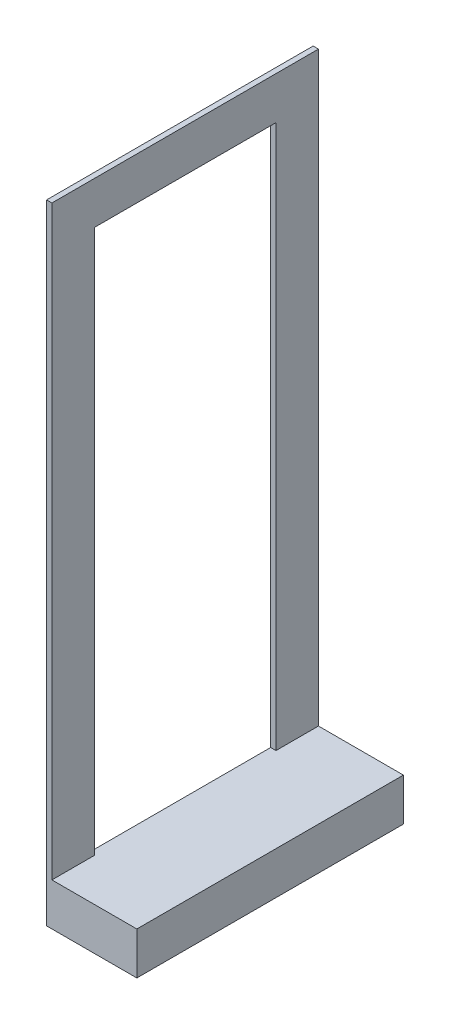
SolidWorks part; units mm, degrees
note: The reader was unsure of these and kept them because the rebuilt part matched: shared geometry of "Sketch1<3>", "Sketch2<2>".
material "6061-T6 AL"
ref_plane "Front" through (0, 0, 0) normal (0, 0, 1) x (1, 0, 0)
ref_plane "Top" through (0, 0, 0) normal (0, 1, 0) x (1, 0, 0)
ref_plane "Right" through (0, 0, 0) normal (1, 0, 0) x (0, 0, -1)
sketch "Sketch1" plane through (179.324, 0, 0) normal (1, 0, 0) x (0, 0, -1)
  line L1 (0, 0) -> (79.7131, 0)
  line L2 (0, 0) -> (0, 188.0306)
  line L3 (0, 188.0306) -> (79.7131, 188.0306)
  line L4 (79.7131, 0) -> (79.7131, 188.0306)
extrude "Extrude-Thin1" add sketch "Sketch1" along normal blind 1.5875 thin thin type one direction reverse wall 12.7
extrude "Extrude-Thin2" add sketch "Sketch1<3>" against normal blind 1.5875 from surface at -179.324 separate body thin thin type one direction reverse wall 12.7
sketch "Sketch1<3>" plane through (179.324, 0, 0) normal (1, 0, 0) x (0, 0, -1) same geometry as "Sketch1"
sketch "Sketch2" plane through (180.9115, 0, 0) normal (1, 0, 0) x (0, 0, -1)
  line L0 (79.7131, 0) -> (79.7131, 188.0306) construction
  line L1 (0, 0) -> (79.7131, 0)
  line L2 (0, 0) -> (0, 12.7)
  line L3 (0, 12.7) -> (79.7131, 12.7)
  line L4 (79.7131, 0) -> (79.7131, 12.7)
  line L5 (12.7, 12.7) -> (67.0131, 12.7) construction
extrude "Boss-Extrude3" add sketch "Sketch2" along normal blind 25.4
extrude "Boss-Extrude4" add sketch "Sketch2<2>" against normal blind 25.4 from surface at -182.499 starting at face at (-1.5875, 94.0153, -39.8566)
sketch "Sketch2<2>" plane through (180.9115, 0, 0) normal (1, 0, 0) x (0, 0, -1) same geometry as "Sketch2"
sketch "Sketch3" plane through (0, 0, 0) normal (1, 0, 0) x (0, 0, -1)
  line L1 (0, 0) -> (117.0761, 0)
  line L2 (0, 0) -> (0, 196.6917)
  line L3 (0, 196.6917) -> (117.0761, 196.6917)
  line L4 (117.0761, 0) -> (117.0761, 196.6917)
extrude "Cut-Extrude1" cut sketch "Sketch3" against normal through all
